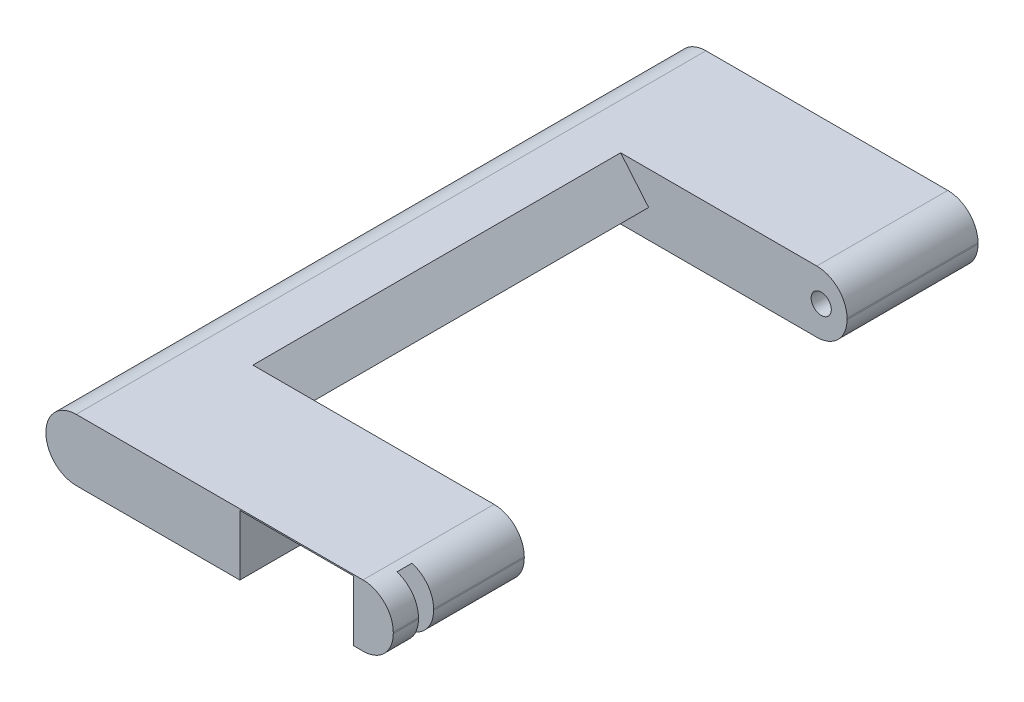
SolidWorks part; units mm, degrees
ref_plane "Alzado" through (0, 0, 0) normal (0, 0, 1) x (1, 0, 0)
ref_plane "Planta" through (0, 0, 0) normal (0, 1, 0) x (1, 0, 0)
ref_plane "Vista lateral" through (0, 0, 0) normal (1, 0, 0) x (0, 0, -1)
sketch "Croquis1" plane through (0, 0, 0) normal (0, 0, 1) x (1, 0, 0)
  line L0 (19.15, 6.05) -> (19.15, -6.2036)
  line L1 (19.15, 6.05) -> (-49.7831, 6.05)
  line L2 (19.15, -6.2036) -> (-49.7831, -6.2036)
  line L3 (-49.7831, 6.05) -> (-49.7831, -6.2036)
  line L4 (11.3, 6.05) -> (15.65, 6.05) construction
  line L5 (16.15, 5.7) -> (16.15, 0.6) construction
  dimension "D1" = 0
  dimension "D2" = 3
extrude "Saliente-Extruir1" add sketch "Croquis1" along normal blind 17 and the other way blind 9 contours L2 L3 L1 L0
sketch "Croquis2" plane through (0, 0, -9) normal (0, 0, -1) x (-1, 0, 0)
  line L0 (49.7831, 6.05) -> (49.7831, -6.2036)
  line L1 (49.7831, 6.05) -> (28.7182, 6.05)
  line L2 (49.7831, -6.2036) -> (28.7182, -6.2036)
  line L3 (28.7182, 6.05) -> (28.7182, -6.2036)
extrude "Saliente-Extruir2" add sketch "Croquis2" along normal blind 99
sketch "Croquis3" plane through (0, 0, -108) normal (0, 0, -1) x (-1, 0, 0)
  line L0 (49.7831, 6.05) -> (49.7831, -6.2036)
  line L1 (49.7831, 6.05) -> (-10.2169, 6.05)
  line L2 (49.7831, -6.2036) -> (-10.2169, -6.2036)
  line L3 (-10.2169, 6.05) -> (-10.2169, -6.2036)
  dimension "D1" = 60
extrude "Saliente-Extruir3" add sketch "Croquis3" against normal blind 26
sketch "Croquis4" plane through (0, 6.05, 0) normal (0, 1, 0) x (1, 0, 0)
  line L0 (19.15, 9) -> (19.15, 9.3851)
  line L1 (19.15, 9.3851) -> (-28.7182, 9.3851)
  line L3 (-49.7831, -17) -> (-49.7831, 108.1402)
  line L4 (-49.7831, 108.1402) -> (84.5445, 108.1402)
  line L5 (84.5445, 108.1402) -> (84.5445, 82.0362)
  line L8 (10.2169, 108) -> (-49.7831, 108)
  line L9 (-49.7831, 108) -> (-49.7831, -17)
  line L10 (-49.7831, -17) -> (19.15, -17)
  line L11 (19.15, -17) -> (19.15, 9)
  line L12 (19.15, 9) -> (-28.7182, 9)
  line L13 (-28.7182, 9) -> (-28.7182, 82)
  line L14 (-28.7182, 82) -> (10.2169, 82)
  line L15 (10.2169, 82) -> (10.2169, 108)
  line L16 (11.3, -0.05) -> (11.3, -17)
  line L17 (11.3, -17) -> (-49.7831, -17)
  line L18 (-49.7831, -17) -> (19.15, -17)
  line L19 (19.15, -17) -> (19.15, 9)
  line L21 (-28.7182, 9.3851) -> (-28.7182, 82.0362)
  line L22 (-28.7182, 82.0362) -> (84.5445, 82.0362)
  dimension "D2" = 90
  dimension "D1" = 0
extrude "Saliente-Extruir4" [suppressed] add sketch "Croquis4" along normal blind 2
fillet "Redondeo1" radius 6 2 edges at (-49.7831, -6.2036, -45.5) (-49.7831, 6.05, -45.5)
chamfer "Chaflán1" distance 6 angle 50 2 edges at (-28.7182, -6.2036, -45.5) (-28.7182, 6.05, -45.5)
sketch "Croquis5" plane through (0, 0, -108) normal (0, 0, -1) x (-1, 0, 0)
  circle A0 centre (-5.1, 0) radius 2
  dimension "D1" = 4
extrude "Cortar-Extruir1" cut sketch "Croquis5" against normal up to next
fillet "Redondeo2" radius 6 4 edges at (19.15, -6.2036, 4) (10.2169, -6.2036, -95) (19.15, 6.05, 4) (10.2169, 6.05, -95)
sketch "Croquis6" plane through (0, -6.2036, 0) normal (0, -1, 0) x (1, 0, 0)
  line L0 (-11.3, 0.05) -> (-11.3, 17)
  line L1 (13.15, 17) -> (-43.7831, 17) construction
  line L2 (11.3, 0.05) -> (11.3, 9)
  line L3 (11.3, 10.5) -> (19.15, 10.5) construction
  line L4 (19.15, 17) -> (19.15, -9) construction
  line L6 (11.3, 15.45) -> (11.3, 9.9) construction
  line L7 (11.3, 9) -> (19.15, 9)
  line L8 (11.3, 12) -> (19.15, 12)
  line L9 (11.3, 12) -> (11.3, 17)
  line L10 (19.15, 12) -> (19.15, 9)
  line L11 (-11.3, 17) -> (11.3, 17)
  line L12 (-11.3, 0.05) -> (11.3, 0.05)
  dimension "D1" = 1.5
  dimension "D2" = 1.5
extrude "Cortar-Extruir2" cut sketch "Croquis6" against normal blind 12
sketch "Croquis7" [suppressed] plane through (0, 8.05, 0) normal (0, 1, 0) x (1, 0, 0)
  line L0 (-43.7831, 107) -> (-43.7831, 45) construction
  line L1 (-43.7831, 107) -> (-43.7831, -17) construction
  line L2 (-43.7831, 45) -> (-43.7831, -17) construction
  line L5 (-43.7831, 45) -> (-35.8687, 45) construction
  line L6 (-35.8687, 10.85) -> (-35.8687, 80) construction
